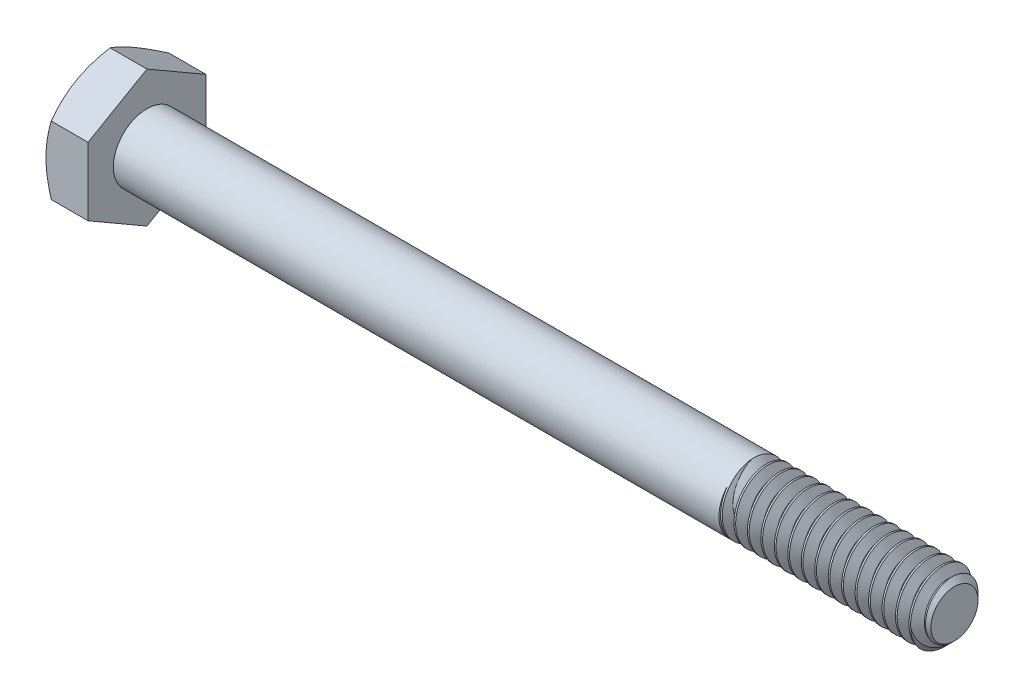
SolidWorks part; units mm, degrees
ref_plane "Front Plane" through (0, 0, 0) normal (0, 0, 1) x (1, 0, 0)
ref_plane "Top Plane" through (0, 0, 0) normal (0, 1, 0) x (1, 0, 0)
ref_plane "Right Plane" through (0, 0, 0) normal (1, 0, 0) x (0, 0, -1)
sketch "Sketch1" plane through (0, 0, 0) normal (0, 0, 1) x (1, 0, 0)
  line L0 (-40.0844, 0) -> (40.0844, 0) construction
  line L1 (40.0844, 3.175) -> (40.0844, -3.175) construction
  line L2 (-36.1156, 5.5563) -> (-36.1156, -5.5563) construction
  line L3 (-40.0844, 5.5562) -> (-40.0844, -5.5562) construction
  point P9 (-36.1156, 0)
  point P10 (35.6394, -3.175)
  dimension "Screw Dia" = 6.35
  dimension "Hex" = 11.1125
  dimension "Head Ht" = 3.9688
  dimension "Screw Lenght" = 76.2
  dimension "D1" = 4.445
ref_plane "Plane2" through (40.0844, 0, 0) normal (1, 0, 0) x (0, 0, -1)
sketch "Sketch5" plane through (40.0844, 0, 0) normal (1, 0, 0) x (0, 0, -1)
  circle A0 centre (0, 0) radius 3.175
extrude "Boss-Extrude3" add sketch "Sketch5" against normal up to vertex (76.2 mm away) up to point (-36.1156, 0, 0)
sketch "Sketch9" plane through (40.0844, 0, 0) normal (1, 0, 0) x (0, 0, -1)
  circle A1 centre (0, 0) radius 3.175
  circle A2 centre (0, 0) radius 3.175
  dimension "D1" = 0
curve "Helix/Spiral1" pitch 1.27 height 20.32 turns 16 parameters "Pitch"=1.27
chamfer "Chamfer1" distance 0.9525 angle 45 1 edges at (40.0844, 0, -3.175)
sketch "Sketch10" plane through (0, 0, 0) normal (0, 0, 1) x (1, 0, 0)
  line L0 (40.0844, 3.175) -> (40.5606, 2.3501)
  line L1 (40.5606, 2.3501) -> (40.7194, 2.3501)
  line L2 (40.7194, 2.3501) -> (41.1956, 3.175)
  line L3 (40.0844, 3.175) -> (41.1956, 3.175)
  line L4 (40.64, 3.175) -> (40.64, 2.3501) construction
  line L5 (40.3225, 2.7626) -> (40.9575, 2.7626) construction
  dimension "D1" = 60
  dimension "D2" = 0.1588
  dimension "D3" = 0.635
sweep "Cut-Sweep1" cut profiles "Sketch10" path "Helix/Spiral1" align with end faces yes
sketch "Sketch11" plane through (0, 0, 0) normal (0, 0, 1) x (1, 0, 0)
  line L0 (-36.1156, 3.175) -> (-36.1156, 0)
  line L1 (-36.1156, 0) -> (24.2094, 0)
  line L3 (24.2094, 0) -> (21.0344, 3.175)
  line L4 (-36.1156, 3.175) -> (21.0344, 3.175)
  dimension "D1" = 45
  dimension "MIn Thread" = 19.05
revolve "Revolve1" add sketch "Sketch11" angle 360 about L1
sketch "Sketch6" plane through (-36.1156, 0, 0) normal (-1, 0, 0) x (0, 0, 1)
  line L0 (0, 5.5563) -> (0, -5.5563) construction
  line L1 (5.5562, 3.2079) -> (0, 6.4158)
  line L2 (0, 6.4158) -> (-5.5562, 3.2079)
  line L3 (-5.5562, 3.2079) -> (-5.5562, -3.2079)
  line L4 (-5.5562, -3.2079) -> (0, -6.4158)
  line L5 (0, -6.4158) -> (5.5562, -3.2079)
  line L6 (5.5562, -3.2079) -> (5.5562, 3.2079)
  circle A0 centre (0, 0) radius 5.5563 construction
extrude "Boss-Extrude4" add sketch "Sketch6" along normal up to vertex (3.9688 mm away) up to point (-40.0844, -5.5562, 0)
sketch "Sketch7" plane through (-40.0844, 0, 0) normal (-1, 0, 0) x (0, 0, 1)
  circle A0 centre (0, 0) radius 5.5563 construction
  circle A1 centre (0, 0) radius 5.5563
sketch "Sketch8" plane through (-40.0844, 0, 0) normal (-1, 0, 0) x (0, 0, 1)
  circle A0 centre (0, 0) radius 5.5563 construction
  circle A1 centre (0, 0) radius 5.5563
extrude "Cut-Extrude3" cut sketch "Sketch8" against normal through all draft 60 flip side to cut
equation "\"D2@Sketch10\" = \"Pitch@Helix/Spiral1\"*.125"
equation "\"D3@Sketch10\" = \"Pitch@Helix/Spiral1\"*.5"
equation "\"D3@Helix/Spiral1\" = \"MIn Thread@Sketch11\"+\"Pitch@Helix/Spiral1\""
equation "\"D1@Chamfer1\" = \"Pitch@Helix/Spiral1\"*.75"
equation "\"D1@Sketch1\" = \"Pitch@Helix/Spiral1\"*3.5"
